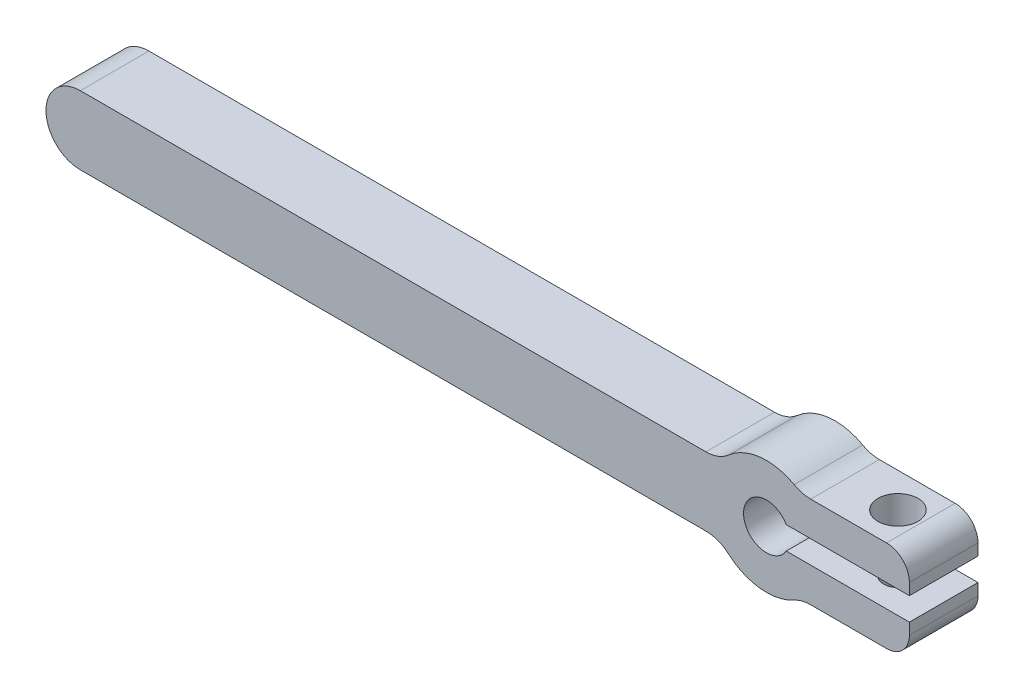
SolidWorks part; units mm, degrees
ref_plane "Front" through (0, 0, 0) normal (0, 0, 1) x (1, 0, 0)
ref_plane "Top" through (0, 0, 0) normal (0, 1, 0) x (1, 0, 0)
ref_plane "Right" through (0, 0, 0) normal (1, 0, 0) x (0, 0, -1)
sketch "Esquisse1" plane through (0, 0, 0) normal (0, 0, 1) x (1, 0, 0)
  circle A0 centre (0, 0) radius 5
  circle A1 centre (0, 0) radius 2
  dimension "D1" = 10
  dimension "D2" = 4
extrude "Boss.-Extru.1" add sketch "Esquisse1" along normal blind 6
sketch "Esquisse2" plane through (0, 0, 6) normal (0, 0, 1) x (1, 0, 0)
  line L0 (-3, 0) -> (0, 0) construction
  line L1 (-63, 3) -> (-3, 3)
  line L2 (-63, 3) -> (-63, -3)
  line L3 (-63, -3) -> (-3, -3)
  line L4 (-3, 3) -> (-3, -3)
  dimension "D1" = 6
  dimension "D2" = 3
  dimension "D3" = 60
extrude "Boss.-Extru.2" add sketch "Esquisse2" against normal up to surface (6 mm away) up to face at (5, 0, 0)
sketch "Esquisse3" plane through (0, 0, 6) normal (0, 0, 1) x (1, 0, 0)
  line L0 (2.5, 0) -> (0, 0) construction
  line L1 (2.5, 4) -> (12.5, 4)
  line L2 (2.5, 4) -> (2.5, -4)
  line L3 (2.5, -4) -> (12.5, -4)
  line L4 (12.5, 4) -> (12.5, -4)
  dimension "D1" = 8
  dimension "D2" = 2.5
  dimension "D3" = 10
extrude "Boss.-Extru.3" add sketch "Esquisse3" against normal up to surface (6 mm away) up to face at (-31.25, 0, 0)
fillet "Congé1" radius 3 6 edges at (-4, 3, 3) (-4, -3, 3) (-63, -3, 3) (-63, 3, 3) (3, -4, 3) (3, 4, 3)
sketch "Esquisse4" plane through (0, 0, 6) normal (0, 0, 1) x (1, 0, 0)
  line L0 (0.5, 0) -> (0, 0) construction
  line L1 (12.5, -1) -> (0.5, -1)
  line L2 (12.5, -1) -> (12.5, 1)
  line L3 (12.5, 1) -> (0.5, 1)
  line L4 (0.5, -1) -> (0.5, 1)
  line L5 (12.5, -4) -> (12.5, 4) construction
  point P7 (0.7837, -0.6077)
  point P8 (0, 0)
  point P9 (12.5, -1.5)
  dimension "D1" = 2
  dimension "D2" = 0.5
extrude "Enlèv. mat.-Extru.1" cut sketch "Esquisse4" against normal through all both and the other way through all
sketch "Esquisse5" plane through (0, 4, 0) normal (0, 1, 0) x (1, 0, 0)
  line L0 (12.5, -3) -> (8.5, -3) construction
  line L1 (12.5, 0) -> (12.5, -6) construction
  circle A0 centre (8.5, -3) radius 1.25
  dimension "D1" = 2.5
  dimension "D2" = 4
extrude "Enlèv. mat.-Extru.2" cut sketch "Esquisse5" against normal through all both and the other way through all
sketch "Esquisse6" plane through (0, 4, 0) normal (0, 1, 0) x (1, 0, 0)
  circle A0 centre (8.5, -3) radius 1.75
  dimension "D1" = 3.5
extrude "Enlèv. mat.-Extru.3" cut sketch "Esquisse6" against normal up to vertex (3 mm away) up to point (12.5, 1, 6)
fillet "Congé2" radius 2 2 edges at (12.5, -4, 3) (12.5, 4, 3)
